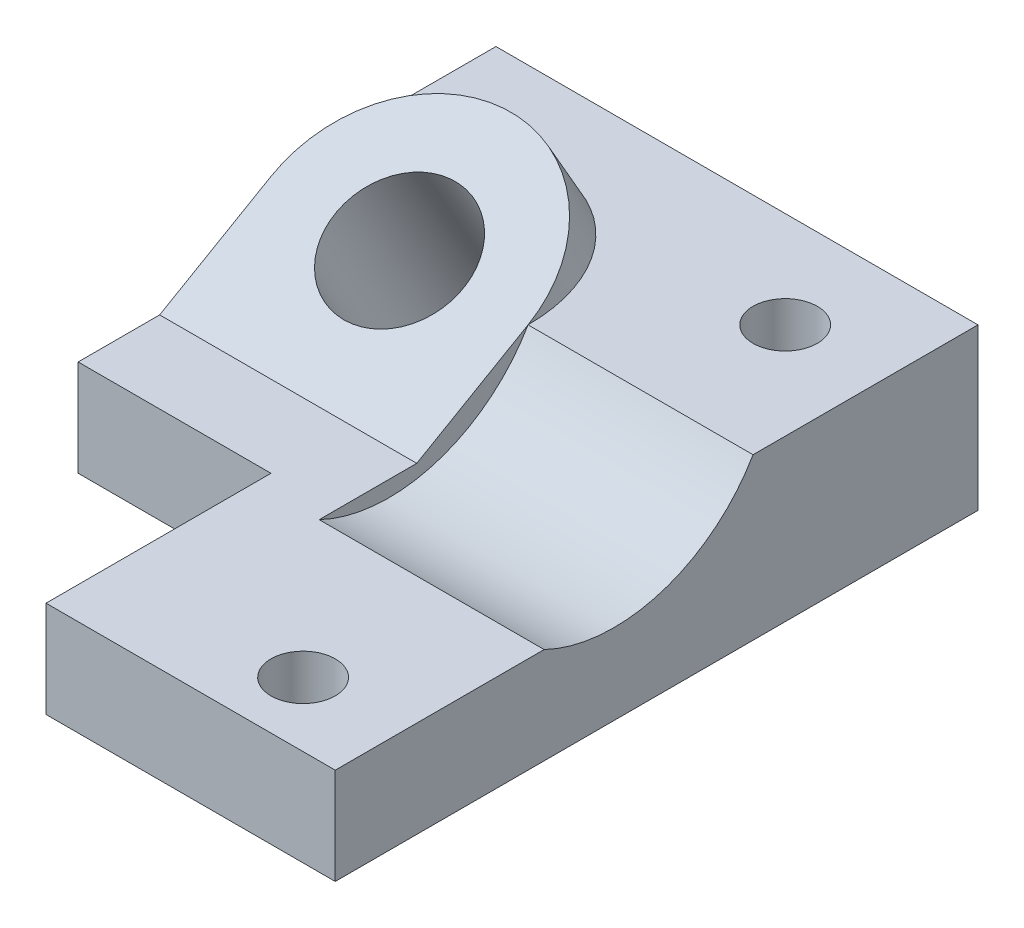
SolidWorks part; units mm, degrees
ref_plane "Front Plane" through (0, 0, 0) normal (0, 0, 1) x (1, 0, 0)
ref_plane "Top Plane" through (0, 0, 0) normal (0, 1, 0) x (1, 0, 0)
ref_plane "Right Plane" through (0, 0, 0) normal (1, 0, 0) x (0, 0, -1)
sketch "Sketch2" plane through (0, 0, 0) normal (1, 0, 0) x (0, 0, -1)
  line L0 (-68.9739, 0) -> (-68.9739, 15)
  line L1 (-68.9739, 15) -> (-3.9739, 15)
  line L2 (-3.9739, 15) -> (-3.9739, 25)
  line L3 (-3.9739, 25) -> (31.0261, 25)
  line L4 (31.0261, 25) -> (31.0261, 0)
  line L5 (31.0261, 0) -> (-68.9739, 0)
  dimension "D4" = 35
  dimension "D1" = 15
  dimension "D2" = 100
  dimension "D3" = 25
extrude "Boss-Extrude1" add sketch "Sketch2" against normal blind 75
sketch "Sketch3" plane through (0, 15, 0) normal (0, 1, 0) x (1, 0, 0)
  line L0 (-75, -68.9739) -> (-75, -33.9739)
  line L1 (-75, -3.9739) -> (-75, -68.9739) construction
  line L2 (-75, -33.9739) -> (-45, -33.9739)
  line L3 (-45, -33.9739) -> (-45, -68.9739)
  line L4 (-75, -68.9739) -> (0, -68.9739) construction
  line L5 (-45, -68.9739) -> (-75, -68.9739)
  dimension "D1" = 30
  dimension "D2" = 35
extrude "Cut-Extrude1" cut sketch "Sketch3" against normal blind 75
sketch "Sketch4" plane through (-75, 0, 0) normal (-1, 0, 0) x (0, 0, 1)
  line L0 (3.9739, 25) -> (21.2944, 15)
  line L1 (3.9739, 15) -> (33.9739, 15) construction
  line L2 (21.2944, 15) -> (3.9739, 15)
  line L3 (3.9739, 15) -> (3.9739, 25)
  dimension "D1" = 150
extrude "Boss-Extrude2" add sketch "Sketch4" against normal blind 40
sketch "Sketch5" plane through (0, 20.4708, 11.8188) normal (0, 0.866, 0.5) x (1, 0, 0)
  line L0 (-75, 9.0585) -> (-35, 9.0585)
  arc A0 (-75, 9.0585) -> (-35, 9.0585) centre (-55, 9.0585) cw
extrude "Boss-Extrude3" add sketch "Sketch5" against normal blind 26
sketch "Sketch6" plane through (0, 20.4708, 11.8188) normal (0, 0.866, 0.5) x (1, 0, 0)
  circle A0 centre (-55, 9.0585) radius 10
  dimension "D1" = 20
extrude "Cut-Extrude2" cut sketch "Sketch6" against normal through all
sketch "Sketch7" plane through (0, 0, 0) normal (1, 0, 0) x (0, 0, -1)
  line L0 (-3.9739, 15) -> (-68.9739, 15) construction
  arc A0 (-3.9739, 25) -> (-36.4739, 15) centre (-25.2239, 36.25) cw
sketch "Sketch8" plane through (0, 0, 0) normal (1, 0, 0) x (0, 0, -1)
  line L0 (-14.7543, 15) -> (-3.9739, 15)
  line L1 (-3.9739, 15) -> (-68.9739, 15) construction
  line L2 (-3.9739, 15) -> (-3.9739, 25)
  line L3 (-36.4739, 15) -> (-21.2944, 15)
  line L4 (-3.9739, 15) -> (-21.2944, 15) construction
  line L5 (-21.2944, 15) -> (-3.9739, 25)
  line L6 (-21.2944, 15) -> (-14.7543, 15)
  arc A0 (-3.9739, 25) -> (-36.4739, 15) centre (-25.6141, 37.5181) cw
  line M4 (-3.9739, 25) -> (-3.9739, 15)
  line M5 (-3.9739, 15) -> (-68.9739, 15)
  dimension "D1" = 25
extrude "Boss-Extrude4" add sketch "Sketch8" against normal blind 37 contours A0 L5 M5 | A0 M4 M5 region at (0, 17.9937, 7.1889) region at (0, 18.6685, 12.2724)
extrude "Cut-Extrude3" cut sketch "Sketch8<3>" against normal blind 35 contours A0 L5 M5 | A0 M5 region at (0, 14.0029, 25.6141) region at (0, 18.6685, 12.2724)
sketch "Sketch8<3>" plane through (0, 0, 0) normal (1, 0, 0) x (0, 0, -1) same geometry as "Sketch8"
sketch "Sketch9" plane through (0, 25, 0) normal (0, 1, 0) x (1, 0, 0)
  line L0 (-75, 31.0261) -> (0, 31.0261) construction
  line L1 (0, 31.0261) -> (0, -3.9739) construction
  line L2 (-45, -68.9739) -> (0, -68.9739) construction
  line L3 (0, -36.4739) -> (0, -68.9739) construction
  circle A0 centre (-15, 16.0261) radius 5
  circle A1 centre (-15, -58.9739) radius 5
  dimension "D1" = 10
  dimension "D2" = 10
  dimension "D3" = 15
  dimension "D4" = 15
  dimension "D5" = 10
  dimension "D6" = 15
extrude "Cut-Extrude4" cut sketch "Sketch9" against normal blind 35
